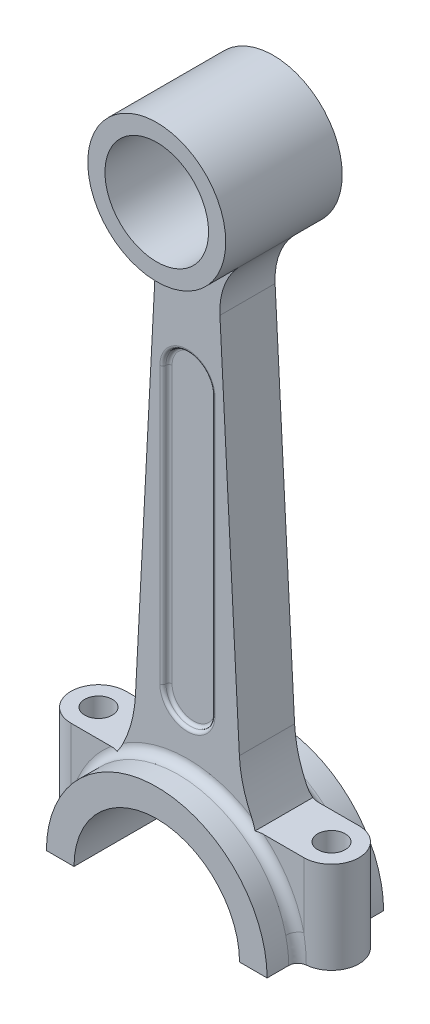
SolidWorks part; units mm, degrees
ref_plane "Front Plane" through (0, 0, 0) normal (0, 0, 1) x (1, 0, 0)
ref_plane "Top Plane" through (0, 0, 0) normal (0, 1, 0) x (1, 0, 0)
ref_plane "Right Plane" through (0, 0, 0) normal (1, 0, 0) x (0, 0, -1)
sketch "Sketch1" plane through (0, 0, 0) normal (0, 0, 1) x (1, 0, 0)
  line L0 (0, 0) -> (0, -201.2) construction
  line L1 (-17.8497, -169.9368) -> (-10, -20.1556)
  line L2 (17.8497, -169.9368) -> (10, -20.1556)
  line L3 (-36, -201.2) -> (-27, -201.2)
  line L4 (27, -201.2) -> (36, -201.2)
  circle A0 centre (0, 0) radius 22.5
  circle A1 centre (0, 0) radius 16.9
  arc A2 (27, -201.2) -> (-27, -201.2) centre (0, -201.2) ccw
  arc A3 (36, -201.2) -> (-36, -201.2) centre (0, -201.2) ccw
  dimension "D1" = 45
  dimension "D2" = 33.8
  dimension "D3" = 72
  dimension "D4" = 54
  dimension "D5" = 20
  dimension "D6" = 201.2
  dimension "D7" = 6
extrude "Boss-Extrude1" add sketch "Sketch1" along normal mid plane 38 contours A3 A2 | A1 A0 | L3 A2 L4 A3 region at (0, -166.005, 0) region at (-11.5231, 18.5805, 0)
extrude "Boss-Extrude2" add sketch "Sketch1<4>" along normal mid plane 18 contours A0 L0 A3 L2 | L0 A0 L1 A3 region at (7.1843, -100.8455, 0) region at (-7.1843, -100.8455, 0)
sketch "Sketch1<4>" plane through (0, 0, 0) normal (0, 0, 1) x (1, 0, 0) same geometry as "Sketch1"
sketch "Sketch2" plane through (0, 0, 9) normal (0, 0, 1) x (1, 0, 0)
  line L0 (0, 0) -> (0, -201.2) construction
  line L1 (0, -145.6) -> (0, -55.6) construction
  line L2 (-8, -145.6) -> (-8, -55.6)
  line L3 (8, -145.6) -> (8, -55.6)
  arc A0 (-8, -145.6) -> (8, -145.6) centre (0, -145.6) ccw
  arc A1 (8, -55.6) -> (-8, -55.6) centre (0, -55.6) ccw
  point P6 (0, -100.6)
  dimension "D2" = 8
  dimension "D1" = 90
extrude "Cut-Extrude1" cut sketch "Sketch2" against normal mid plane 4
mirror "Mirror2" about plane through (0, 0, 0) normal (0, 0, 1) of "Cut-Extrude1"
fillet "Fillet1" radius 1 16 edges at (0, -153.6, -9) (8, -100.6, -9) (0, -47.6, -9) (0, -47.6, 9) (8, -100.6, 9) (0, -153.6, 9) (8, -100.6, -7) (0, -47.6, -7) (-8, -100.6, -7) (0, -153.6, -7) (-8, -100.6, 7) (0, -47.6, 7) (8, -100.6, 7) (0, -153.6, 7) (-8, -100.6, -9) (-8, -100.6, 9)
ref_plane "Plane1" through (0, -171.2, 0) normal (0, -1, 0) x (-1, 0, 0)
fillet "Fillet2" radius 40 2 edges at (17.8497, -169.9368, 0) (-17.8497, -169.9368, 0)
fillet "Fillet3" radius 22.5 2 edges at (-10, -20.1556, 0) (10, -20.1556, 0)
sketch "Sketch3" plane through (0, -171.2, 0) normal (0, -1, 0) x (-1, 0, 0)
  line L0 (38, 0) -> (-38, 0) construction
  line L1 (38, -9) -> (-38, -9)
  line L2 (38, 9) -> (-38, 9)
  arc A0 (38, -9) -> (38, 9) centre (38, 0) ccw
  arc A1 (-38, 9) -> (-38, -9) centre (-38, 0) ccw
  point P2 (0, 0)
  point P8 (0, 0)
  point P9 (0, 0)
  dimension "D2" = 9
  dimension "D1" = 76
extrude "Boss-Extrude3" add sketch "Sketch3" along normal up to surface (30 mm away) up to face at (-31.5, -201.2, 0)
sketch "Sketch4" plane through (0, 0, 9) normal (0, 0, 1) x (1, 0, 0)
  line L1 (-27, -201.2) -> (27, -201.2)
  line L2 (-27, -201.2) -> (27, -201.2)
  arc A1 (27, -201.2) -> (-27, -201.2) centre (0, -201.2) ccw
  arc A2 (27, -201.2) -> (-27, -201.2) centre (0, -201.2) ccw
  dimension "D1" = 0
extrude "Cut-Extrude2" cut sketch "Sketch4" against normal through all
sketch "Sketch5" plane through (0, -171.2, 0) normal (0, 1, 0) x (1, 0, 0)
  circle A0 centre (38, 0) radius 4.5
  circle A1 centre (-38, 0) radius 4.5
  dimension "D1" = 9
extrude "Cut-Extrude3" cut sketch "Sketch5" against normal through all
fillet "Fillet4" radius 3 2 edges at (0, -165.2, 9) (0, -165.2, -9)
